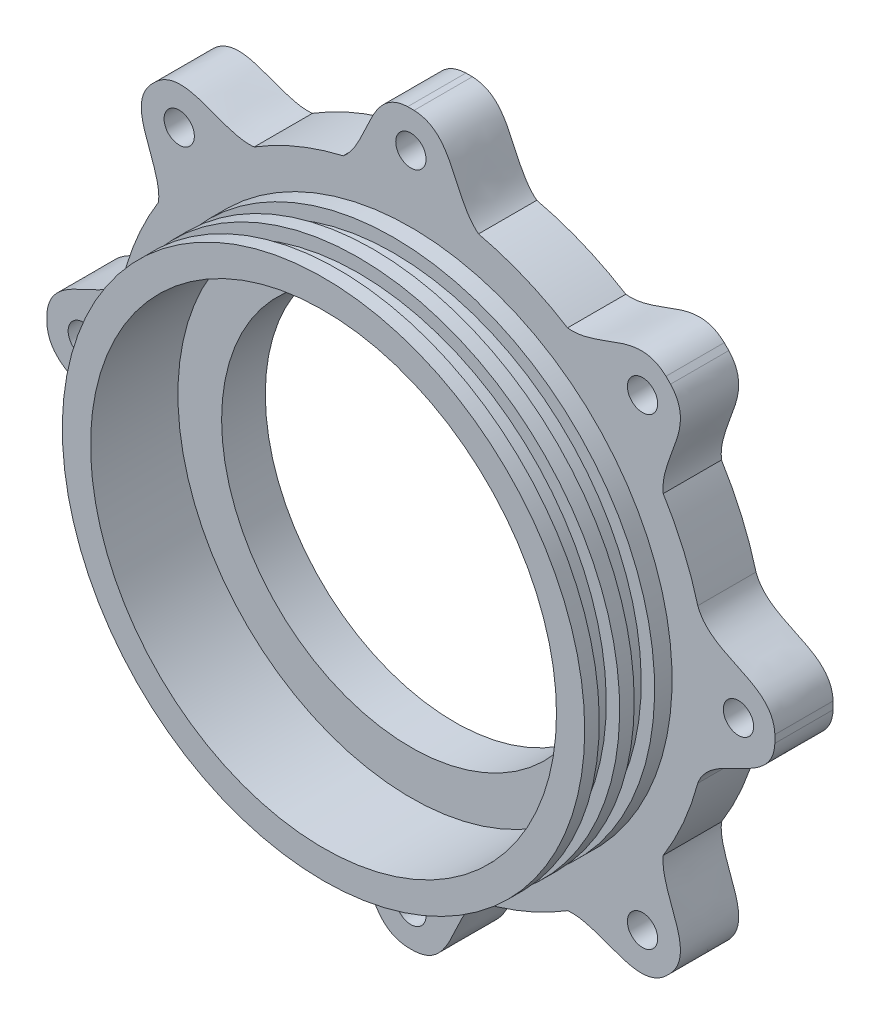
SolidWorks part; units mm, degrees
material "6063-T6"
ref_plane "Front Plane" through (0, 0, 0) normal (0, 0, 1) x (1, 0, 0)
ref_plane "Top Plane" through (0, 0, 0) normal (0, 1, 0) x (1, 0, 0)
ref_plane "Right Plane" through (0, 0, 0) normal (1, 0, 0) x (0, 0, -1)
sketch "Sketch1" plane through (0, 0, 0) normal (0, 0, 1) x (1, 0, 0)
  circle A0 centre (0, 0) radius 44.85
  circle A1 centre (0, 0) radius 45.15 construction
  dimension "D1" = 89.7
  dimension "D2" = 90.3
  dimension "D3" = 0.3
extrude "Boss-Extrude1" add sketch "Sketch1" along normal blind 15
sketch "Sketch2" plane through (0, 0, 0) normal (0, 0, -1) x (-1, 0, 0)
  circle A0 centre (0, 0) radius 62.5
  circle A1 centre (0, 0) radius 50 construction
  dimension "D1" = 125
  dimension "D2" = 100
extrude "Boss-Extrude2" add sketch "Sketch2" along normal blind 10
sketch "Sketch3" plane through (0, 0, 15) normal (0, 0, 1) x (1, 0, 0)
  circle A0 centre (0, 0) radius 40
  dimension "D1" = 80
extrude "Cut-Extrude1" cut sketch "Sketch3" against normal blind 15
sketch "Sketch4" plane through (0, 0, 0) normal (1, 0, 0) x (0, 0, -1)
  line L0 (42.7131, 0) -> (-42.7131, 0) construction
  line L1 (-48.1647, 45.15) -> (43.8613, 45.15) construction
  line L2 (-15, 44.85) -> (-15, -44.85) construction
  line L3 (0, 62.5) -> (0, -62.5) construction
  line L4 (-7.5, 59.1563) -> (-7.5, -7.7145) construction
  line L5 (-3, 46.2748) -> (-6.5, 42.55) construction
  line L6 (-6.5, 46.2748) -> (-3, 46.2748)
  line L7 (-6.5, 46.2748) -> (-6.5, 42.55)
  line L8 (-6.5, 42.55) -> (-3, 42.55)
  line L9 (-3, 46.2748) -> (-3, 42.55)
  line L10 (-12.5, 46.2748) -> (-9, 46.2748)
  line L11 (-12.5, 46.2748) -> (-12.5, 42.55)
  line L12 (-12.5, 42.55) -> (-9, 42.55)
  line L13 (-9, 46.2748) -> (-9, 42.55)
  line L14 (-6.5, 46.2748) -> (-3, 42.55) construction
  line L15 (-4.75, 47.8445) -> (-4.75, 41.4736) construction
  circle A0 centre (-4.75, 44.05) radius 1.5 construction
  point P5 (0, 0)
  point P24 (-4.75, 44.4124)
  dimension "D5" = 3.5
  dimension "D1" = 45.15
  dimension "D2" = 15
  dimension "D3" = 7.5
  dimension "D4" = 3.5
  dimension "D6" = 2.5
  dimension "D7" = 2.5
  dimension "D8" = 3
  dimension "D9" = 2.6
revolve "Cut-Revolve1" cut sketch "Sketch4" angle 360 about L0
sketch "Sketch5" plane through (0, 0, 0) normal (0, 0, 1) x (1, 0, 0)
  circle A0 centre (0, 0) radius 44.75 construction
  circle A1 centre (0, 0) radius 50 construction
  circle A2 centre (0, 0) radius 46
  circle A3 centre (0, 0) radius 48.8
  dimension "D1" = 89.5
  dimension "D2" = 100
  dimension "D3" = 97.6
  dimension "D4" = 92
  dimension "D5" = 2.8
extrude "Cut-Extrude2" [suppressed] cut sketch "Sketch5" against normal blind 1.5
sketch "Sketch7" plane through (0, 0, -10) normal (0, 0, -1) x (-1, 0, 0)
  line L0 (0, 0) -> (81.7368, 0) construction
  line L1 (50, -30.8838) -> (50, 30.8838) construction
  circle A0 centre (0, 0) radius 44.75 construction
  circle A1 centre (0, 0) radius 50 construction
  circle A3 centre (0, 0) radius 62.5 construction
  circle A4 centre (56.25, 0) radius 2.6
  circle A5 centre (56.25, 0) radius 5 construction
  point P12 (50, 0)
  dimension "D1" = 89.5
  dimension "D2" = 100
  dimension "D3" = 125
  dimension "D4" = 5.2
  dimension "D5" = 10
  dimension "D6" = 6.25
extrude "Cut-Extrude4" cut sketch "Sketch7" against normal through all
ref_axis "Axis1" through (0, 0, -45.8748) along (0, 0, 1)
pattern_circular "CirPattern1" count 8 over 360 about axis through (0, 0, -45.8748) along (0, 0, 1) of "Cut-Extrude4"
sketch "Sketch9" plane through (0, 0, -10) normal (0, 0, -1) x (-1, 0, 0)
  circle A0 centre (0, 0) radius 37.5
  circle A2 centre (0, 0) radius 37 construction
  dimension "D1" = 75
  dimension "D3" = 74
extrude "Cut-Extrude6" cut sketch "Sketch9" against normal blind 2.5
sketch "Sketch10" plane through (0, 0, -7.5) normal (0, 0, -1) x (-1, 0, 0)
  circle A0 centre (0, 0) radius 32.5
  dimension "D1" = 65
extrude "Cut-Extrude7" cut sketch "Sketch10" against normal through all
sketch "Sketch13" [suppressed] plane through (0, 0, -7.5) normal (0, 0, -1) x (-1, 0, 0)
  line L1 (-27.2638, 37.5) -> (27.2638, 37.5) construction
  circle A0 centre (0, 0) radius 33.85
  circle A1 centre (0, 0) radius 36.15
  circle A2 centre (0, 0) radius 35 construction
  circle A4 centre (0, 0) radius 32.5 construction
  point P11 (0.1556, 0)
  point P14 (0, 37.5)
  dimension "D1" = 2.3
  dimension "D2" = 1.35
extrude "Cut-Extrude9" [suppressed] cut sketch "Sketch13" against normal blind 1.2
sketch "Sketch14" plane through (0, 0, -10) normal (0, 0, -1) x (-1, 0, 0)
  line L0 (0, 0) -> (93.6112, 0) construction
  line L1 (37.5, -16.12) -> (37.5, 16.12) construction
  circle A0 centre (0, 0) radius 43.5 construction
  circle A1 centre (0, 0) radius 37.5 construction
  circle A2 centre (40.5, 0) radius 1.6
  point P11 (37.5, 0)
  dimension "D1" = 87
  dimension "D2" = 75
  dimension "D3" = 3.2
  dimension "D4" = 3
extrude "Cut-Extrude10" [suppressed] cut sketch "Sketch14" against normal blind 5
pattern_circular "CirPattern2" [suppressed] count 12 over 360 about axis through (0, 0, -45.8748) along (0, 0, 1) of bodies 140
sketch "Sketch15" plane through (0, 0, 0) normal (0, 0, 1) x (1, 0, 0)
  circle A2 centre (0, 0) radius 36.25 construction
  circle A4 centre (-36.25, 0) radius 1.6
  point P6 (0, 0)
  dimension "D1" = 72.5
  dimension "D2" = 3.2
extrude "Cut-Extrude11" [suppressed] cut sketch "Sketch15" against normal blind 5
pattern_circular "CirPattern3" [suppressed] count 4 over 360 about axis through (0, 0, -45.8748) along (0, 0, 1) of bodies 155
sketch "Sketch16" plane through (0, 0, 0) normal (0, 0, 1) x (1, 0, 0)
  line L0 (0, 0) -> (68.6264, 0) construction
  line L1 (56.25, 0) -> (56.25, 7.5) construction
  line L2 (56.25, 0) -> (60.8462, 4.5962) construction
  line L3 (0, 0) -> (49.2622, 13.1998) construction
  circle A0 centre (0, 0) radius 51
  circle A1 centre (0, 0) radius 62.5 construction
  circle A2 centre (0, 0) radius 63
  spline S0 degree 3 poles (62.5, 0) (62.771, 8.083) (51.6285, 6.7243) (49.2622, 13.1998) knots 0 0 0 0 1 1 1 1
  spline S1 degree 3 poles (62.5, 0) (62.771, -8.083) (51.6285, -6.7243) (49.2622, -13.1998) knots 0 0 0 0 1 1 1 1
  spline S2 degree 3 poles (44.1942, -44.1942) (50.1228, -38.5893) (41.2596, -31.5162) (43.7343, -25.25) knots 0 0 0 0 1 1 1 1
  spline S3 degree 3 poles (44.1942, -44.1942) (38.5893, -50.1228) (31.5162, -41.2596) (25.25, -43.7343) knots 0 0 0 0 1 1 1 1
  spline S4 degree 3 poles (0, -62.5) (8.1554, -62.7289) (6.8897, -51.4602) (13.0704, -48.7793) knots 0 0 0 0 1 1 1 1
  spline S5 degree 3 poles (0, -62.5) (-8.1554, -62.7289) (-6.8897, -51.4602) (-13.0704, -48.7793) knots 0 0 0 0 1 1 1 1
  spline S6 degree 3 poles (-44.1942, -44.1942) (-38.5893, -50.1228) (-31.5162, -41.2596) (-25.25, -43.7343) knots 0 0 0 0 1 1 1 1
  spline S7 degree 3 poles (-44.1942, -44.1942) (-50.1228, -38.5893) (-41.2596, -31.5162) (-43.7343, -25.25) knots 0 0 0 0 1 1 1 1
  spline S8 degree 3 poles (-62.5, 0) (-62.7289, -8.1554) (-51.4602, -6.8897) (-48.7793, -13.0704) knots 0 0 0 0 1 1 1 1
  spline S9 degree 3 poles (-62.5, 0) (-62.7289, 8.1554) (-51.4602, 6.8897) (-48.7793, 13.0704) knots 0 0 0 0 1 1 1 1
  spline S10 degree 3 poles (-44.1942, 44.1942) (-50.1228, 38.5893) (-41.2596, 31.5162) (-43.7343, 25.25) knots 0 0 0 0 1 1 1 1
  spline S11 degree 3 poles (-44.1942, 44.1942) (-38.5893, 50.1228) (-31.5162, 41.2596) (-25.25, 43.7343) knots 0 0 0 0 1 1 1 1
  spline S12 degree 3 poles (0, 62.5) (-8.1554, 62.7289) (-6.8897, 51.4602) (-13.0704, 48.7793) knots 0 0 0 0 1 1 1 1
  spline S13 degree 3 poles (0, 62.5) (8.1554, 62.7289) (6.8897, 51.4602) (13.0704, 48.7793) knots 0 0 0 0 1 1 1 1
  spline S14 degree 3 poles (44.1942, 44.1942) (38.5893, 50.1228) (31.5162, 41.2596) (25.25, 43.7343) knots 0 0 0 0 1 1 1 1
  spline S15 degree 3 poles (44.1942, 44.1942) (50.1228, 38.5893) (41.2596, 31.5162) (43.7343, 25.25) knots 0 0 0 0 1 1 1 1
  point P69 (0, 0)
  dimension "D1" = 102
  dimension "D3" = 7.5
  dimension "D5" = 126
  dimension "D2" = 15
  dimension "D4" = 6.5
extrude "Cut-Extrude12" cut sketch "Sketch16" against normal blind 10 contours S14 A2 S13 A0 | A2 S15 A0 S0 | S2 A2 S1 A0 | S4 A2 S3 A0 | S6 A2 S5 A0 | S8 A2 S7 A0 | S10 A2 S9 A0 | S12 A2 S11 A0 region at (-62.8218, 0, 0)
